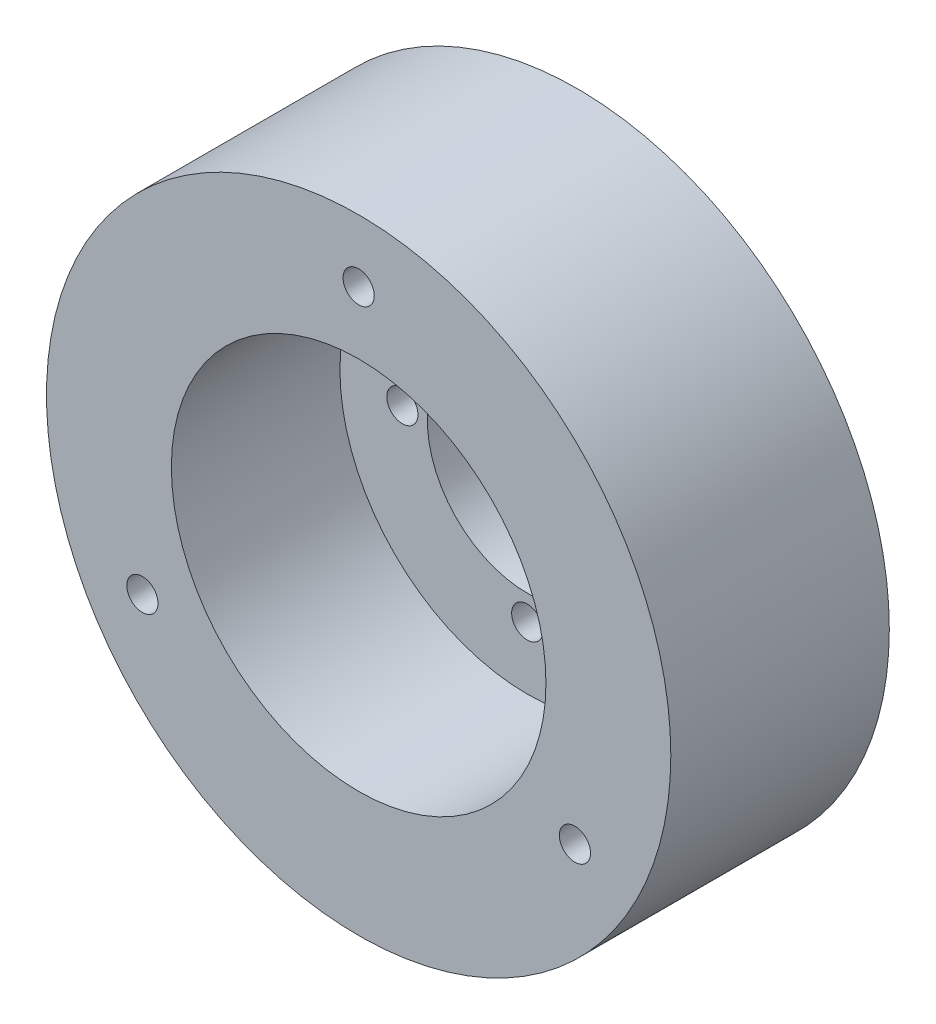
SolidWorks part; units mm, degrees
ref_plane "Front Plane" through (0, 0, 0) normal (0, 0, 1) x (1, 0, 0)
ref_plane "Top Plane" through (0, 0, 0) normal (0, 1, 0) x (1, 0, 0)
ref_plane "Right Plane" through (0, 0, 0) normal (1, 0, 0) x (0, 0, -1)
sketch "Sketch1" plane through (0, 0, 0) normal (0, 0, 1) x (1, 0, 0)
  circle A0 centre (0, 0) radius 50
  circle A1 centre (0, 0) radius 16
  dimension "D1" = 100
extrude "Boss-Extrude1" add sketch "Sketch1" along normal blind 8
sketch "Sketch2" plane through (0, 0, 8) normal (0, 0, 1) x (1, 0, 0)
  circle A0 centre (0, 0) radius 50
  circle A1 centre (0, 0) radius 30
  dimension "D1" = 20
  dimension "D2" = 100
extrude "Boss-Extrude2" add sketch "Sketch2" along normal up to surface (27 mm away) up to face at (50, 0, 0)
sketch "Sketch3" plane through (0, 0, 35) normal (0, 0, 1) x (1, 0, 0)
  circle A0 centre (0, 40) radius 2.5
  circle A1 centre (34.641, -20) radius 2.5
  circle A2 centre (-34.641, -20) radius 2.5
extrude "Cut-Extrude1" cut sketch "Sketch3" against normal through all
sketch "Sketch4" plane through (0, 0, 8) normal (0, 0, 1) x (1, 0, 0)
  circle A0 centre (0, 20) radius 2.5
  circle A1 centre (20, 0) radius 2.5
  circle A2 centre (0, -20) radius 2.5
  circle A3 centre (-20, 0) radius 2.5
  dimension "D1" = 5
  dimension "D2" = 4
extrude "Cut-Extrude2" cut sketch "Sketch4" against normal through all
